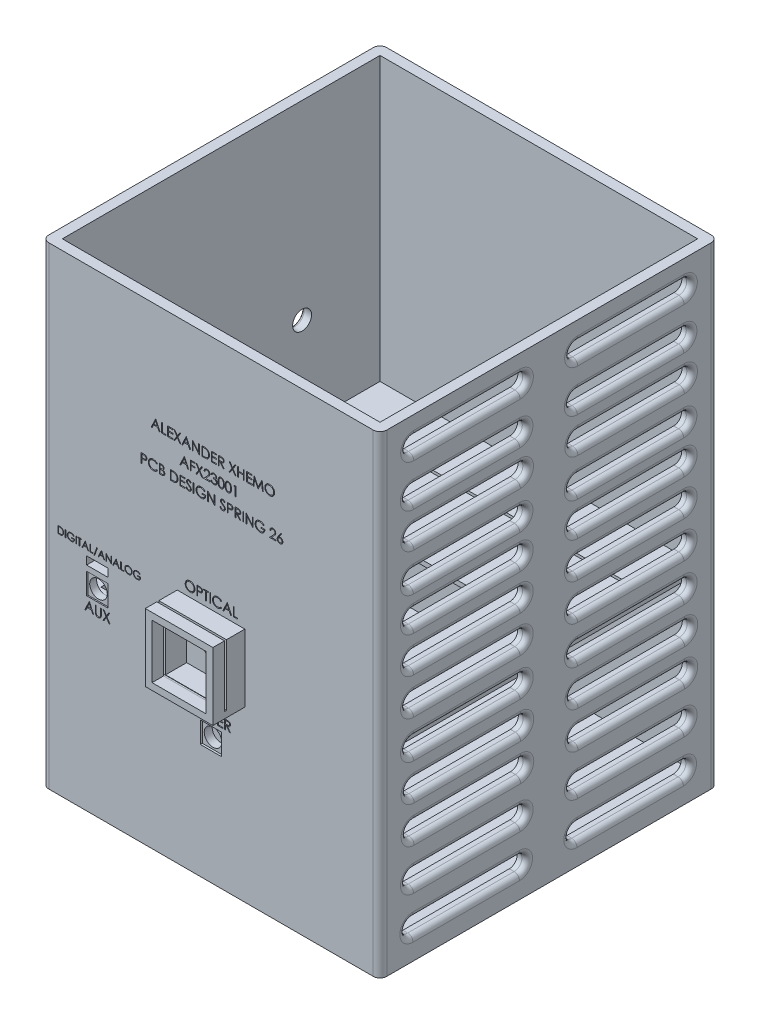
SolidWorks part; units mm, degrees
ref_plane "Front Plane" through (0, 0, 0) normal (0, 0, 1) x (1, 0, 0)
ref_plane "Top Plane" through (0, 0, 0) normal (0, 1, 0) x (1, 0, 0)
ref_plane "Right Plane" through (0, 0, 0) normal (1, 0, 0) x (0, 0, -1)
sketch "Sketch1" plane through (0, 0, 0) normal (0, 1, 0) x (1, 0, 0)
  line L1 (-58.7434, 32.2257) -> (68.2566, 32.2257)
  line L2 (-58.7434, 32.2257) -> (-58.7434, -94.7743)
  line L3 (-58.7434, -94.7743) -> (68.2566, -94.7743)
  line L4 (68.2566, 32.2257) -> (68.2566, -94.7743)
  dimension "D1" = 127
  dimension "D2" = 127
extrude "Boss-Extrude1" add sketch "Sketch1" along normal blind 177.8
sketch "Sketch2" plane through (0, 177.8, 0) normal (0, 1, 0) x (1, 0, 0)
  line L0 (68.2566, 32.2257) -> (-58.7434, 32.2257) construction
  line L1 (-54.9334, 28.4157) -> (64.4466, 28.4157)
  line L2 (-54.9334, 28.4157) -> (-54.9334, -90.9643)
  line L3 (-54.9334, -90.9643) -> (64.4466, -90.9643)
  line L4 (64.4466, 28.4157) -> (64.4466, -90.9643)
  line L5 (-58.7434, 32.2257) -> (-58.7434, -94.7743) construction
  line L6 (68.2566, -94.7743) -> (68.2566, 32.2257) construction
  line L7 (-58.7434, -94.7743) -> (68.2566, -94.7743) construction
  dimension "D1" = 3.81
  dimension "D2" = 3.81
  dimension "D3" = 3.81
  dimension "D4" = 3.81
extrude "Cut-Extrude1" cut sketch "Sketch2" against normal blind 173.99 contours L2 L1 L4 L3
sketch "Sketch3" plane through (68.2566, 0, 0) normal (1, 0, 0) x (0, 0, -1)
  line L6 (-20.4535, 167.6868) -> (19.5465, 167.6868) construction
  line L8 (-82.0743, 167.6822) -> (-42.0743, 167.6822) construction
  line L9 (-82.0743, 170.6109) -> (-42.0743, 170.6109)
  line L10 (-82.0743, 164.7535) -> (-42.0743, 164.7535)
  line L12 (-20.4535, 170.6155) -> (19.5465, 170.6155)
  line L13 (-20.4535, 164.7581) -> (19.5465, 164.7581)
  line L14 (-20.3906, 138.5625) -> (19.6094, 138.5625) construction
  line L15 (-82.0115, 138.558) -> (-42.0115, 138.558) construction
  line L16 (-20.6092, 151.8967) -> (19.3908, 151.8967) construction
  line L17 (-82.2301, 151.8921) -> (-42.2301, 151.8921) construction
  line L18 (-82.2301, 154.8207) -> (-42.2301, 154.8207)
  line L19 (-82.2301, 148.9634) -> (-42.2301, 148.9634)
  line L20 (-20.6092, 154.8253) -> (19.3908, 154.8253)
  line L21 (-20.6092, 148.968) -> (19.3908, 148.968)
  line L22 (-82.0115, 141.4866) -> (-42.0115, 141.4866)
  line L23 (-82.0115, 135.6293) -> (-42.0115, 135.6293)
  line L24 (-20.3906, 141.4912) -> (19.6094, 141.4912)
  line L25 (-20.3906, 135.6339) -> (19.6094, 135.6339)
  line L26 (-20.6092, 124.3541) -> (19.3908, 124.3541) construction
  line L27 (-82.2301, 124.3495) -> (-42.2301, 124.3495) construction
  line L28 (-82.2301, 127.2781) -> (-42.2301, 127.2781)
  line L29 (-82.2301, 121.4208) -> (-42.2301, 121.4208)
  line L30 (-20.6092, 127.2827) -> (19.3908, 127.2827)
  line L31 (-20.6092, 121.4254) -> (19.3908, 121.4254)
  line L32 (-20.5154, 111.5408) -> (19.4846, 111.5408) construction
  line L33 (-82.1363, 111.5362) -> (-42.1363, 111.5362) construction
  line L34 (-82.1363, 114.4648) -> (-42.1363, 114.4648)
  line L35 (-82.1363, 108.6075) -> (-42.1363, 108.6075)
  line L36 (-20.5154, 114.4694) -> (19.4846, 114.4694)
  line L37 (-20.5154, 108.6121) -> (19.4846, 108.6121)
  line L38 (-20.5154, 97.9879) -> (19.4846, 97.9879) construction
  line L39 (-82.1363, 97.9833) -> (-42.1363, 97.9833) construction
  line L40 (-82.1363, 100.912) -> (-42.1363, 100.912)
  line L41 (-82.1363, 95.0547) -> (-42.1363, 95.0547)
  line L42 (-20.5154, 100.9166) -> (19.4846, 100.9166)
  line L43 (-20.5154, 95.0593) -> (19.4846, 95.0593)
  line L44 (-20.5154, 84.2199) -> (19.4846, 84.2199) construction
  line L45 (-82.1363, 84.2153) -> (-42.1363, 84.2153) construction
  line L46 (-82.1363, 87.144) -> (-42.1363, 87.144)
  line L47 (-82.1363, 81.2867) -> (-42.1363, 81.2867)
  line L48 (-20.5154, 87.1486) -> (19.4846, 87.1486)
  line L49 (-20.5154, 81.2913) -> (19.4846, 81.2913)
  line L50 (-20.5154, 70.0217) -> (19.4846, 70.0217) construction
  line L51 (-82.1363, 70.0171) -> (-42.1363, 70.0171) construction
  line L52 (-82.1363, 72.9458) -> (-42.1363, 72.9458)
  line L53 (-82.1363, 67.0885) -> (-42.1363, 67.0885)
  line L54 (-20.5154, 72.9504) -> (19.4846, 72.9504)
  line L55 (-20.5154, 67.0931) -> (19.4846, 67.0931)
  line L56 (-20.3003, 56.2537) -> (19.6997, 56.2537) construction
  line L57 (-81.9211, 56.2491) -> (-41.9211, 56.2491) construction
  line L58 (-81.9211, 59.1778) -> (-41.9211, 59.1778)
  line L59 (-81.9211, 53.3205) -> (-41.9211, 53.3205)
  line L60 (-20.3003, 59.1824) -> (19.6997, 59.1824)
  line L61 (-20.3003, 53.3251) -> (19.6997, 53.3251)
  line L62 (-20.3003, 42.4858) -> (19.6997, 42.4858) construction
  line L63 (-81.9211, 42.4812) -> (-41.9211, 42.4812) construction
  line L64 (-81.9211, 45.4098) -> (-41.9211, 45.4098)
  line L65 (-81.9211, 39.5525) -> (-41.9211, 39.5525)
  line L66 (-20.3003, 45.4144) -> (19.6997, 45.4144)
  line L67 (-20.3003, 39.5571) -> (19.6997, 39.5571)
  line L68 (-20.5436, 26.9383) -> (19.4564, 26.9383) construction
  line L69 (-82.1645, 26.9337) -> (-42.1645, 26.9337) construction
  line L86 (-82.1645, 29.8624) -> (-42.1645, 29.8624)
  line L87 (-82.1645, 24.005) -> (-42.1645, 24.005)
  line L88 (-20.5436, 29.867) -> (19.4564, 29.867)
  line L89 (-20.5436, 24.0096) -> (19.4564, 24.0096)
  line L90 (-20.7544, 11.1247) -> (19.2456, 11.1247) construction
  line L91 (-82.3753, 11.1201) -> (-42.3753, 11.1201) construction
  line L96 (-82.3753, 14.0488) -> (-42.3753, 14.0488)
  line L97 (-82.3753, 8.1915) -> (-42.3753, 8.1915)
  line L98 (-20.7544, 14.0534) -> (19.2456, 14.0534)
  line L99 (-20.7544, 8.1961) -> (19.2456, 8.1961)
  arc A0 (-82.0743, 170.6109) -> (-82.0743, 164.7535) centre (-82.0743, 167.6822) ccw
  arc A1 (-42.0743, 164.7535) -> (-42.0743, 170.6109) centre (-42.0743, 167.6822) ccw
  arc A2 (-20.4535, 170.6155) -> (-20.4535, 164.7581) centre (-20.4535, 167.6868) ccw
  arc A3 (19.5465, 164.7581) -> (19.5465, 170.6155) centre (19.5465, 167.6868) ccw
  arc A4 (-82.2301, 154.8207) -> (-82.2301, 148.9634) centre (-82.2301, 151.8921) ccw
  arc A5 (-42.2301, 148.9634) -> (-42.2301, 154.8207) centre (-42.2301, 151.8921) ccw
  arc A6 (-20.6092, 154.8253) -> (-20.6092, 148.968) centre (-20.6092, 151.8967) ccw
  arc A7 (19.3908, 148.968) -> (19.3908, 154.8253) centre (19.3908, 151.8967) ccw
  arc A8 (-82.0115, 141.4866) -> (-82.0115, 135.6293) centre (-82.0115, 138.558) ccw
  arc A9 (-42.0115, 135.6293) -> (-42.0115, 141.4866) centre (-42.0115, 138.558) ccw
  arc A10 (-20.3906, 141.4912) -> (-20.3906, 135.6339) centre (-20.3906, 138.5625) ccw
  arc A11 (19.6094, 135.6339) -> (19.6094, 141.4912) centre (19.6094, 138.5625) ccw
  arc A12 (-82.2301, 127.2781) -> (-82.2301, 121.4208) centre (-82.2301, 124.3495) ccw
  arc A13 (-42.2301, 121.4208) -> (-42.2301, 127.2781) centre (-42.2301, 124.3495) ccw
  arc A14 (-20.6092, 127.2827) -> (-20.6092, 121.4254) centre (-20.6092, 124.3541) ccw
  arc A15 (19.3908, 121.4254) -> (19.3908, 127.2827) centre (19.3908, 124.3541) ccw
  arc A16 (-82.1363, 114.4648) -> (-82.1363, 108.6075) centre (-82.1363, 111.5362) ccw
  arc A17 (-42.1363, 108.6075) -> (-42.1363, 114.4648) centre (-42.1363, 111.5362) ccw
  arc A18 (-20.5154, 114.4694) -> (-20.5154, 108.6121) centre (-20.5154, 111.5408) ccw
  arc A19 (19.4846, 108.6121) -> (19.4846, 114.4694) centre (19.4846, 111.5408) ccw
  arc A20 (-82.1363, 100.912) -> (-82.1363, 95.0547) centre (-82.1363, 97.9833) ccw
  arc A21 (-42.1363, 95.0547) -> (-42.1363, 100.912) centre (-42.1363, 97.9833) ccw
  arc A22 (-20.5154, 100.9166) -> (-20.5154, 95.0593) centre (-20.5154, 97.9879) ccw
  arc A23 (19.4846, 95.0593) -> (19.4846, 100.9166) centre (19.4846, 97.9879) ccw
  arc A24 (-82.1363, 87.144) -> (-82.1363, 81.2867) centre (-82.1363, 84.2153) ccw
  arc A25 (-42.1363, 81.2867) -> (-42.1363, 87.144) centre (-42.1363, 84.2153) ccw
  arc A26 (-20.5154, 87.1486) -> (-20.5154, 81.2913) centre (-20.5154, 84.2199) ccw
  arc A27 (19.4846, 81.2913) -> (19.4846, 87.1486) centre (19.4846, 84.2199) ccw
  arc A28 (-82.1363, 72.9458) -> (-82.1363, 67.0885) centre (-82.1363, 70.0171) ccw
  arc A29 (-42.1363, 67.0885) -> (-42.1363, 72.9458) centre (-42.1363, 70.0171) ccw
  arc A30 (-20.5154, 72.9504) -> (-20.5154, 67.0931) centre (-20.5154, 70.0217) ccw
  arc A31 (19.4846, 67.0931) -> (19.4846, 72.9504) centre (19.4846, 70.0217) ccw
  arc A32 (-81.9211, 59.1778) -> (-81.9211, 53.3205) centre (-81.9211, 56.2491) ccw
  arc A33 (-41.9211, 53.3205) -> (-41.9211, 59.1778) centre (-41.9211, 56.2491) ccw
  arc A34 (-20.3003, 59.1824) -> (-20.3003, 53.3251) centre (-20.3003, 56.2537) ccw
  arc A35 (19.6997, 53.3251) -> (19.6997, 59.1824) centre (19.6997, 56.2537) ccw
  arc A36 (-81.9211, 45.4098) -> (-81.9211, 39.5525) centre (-81.9211, 42.4812) ccw
  arc A37 (-41.9211, 39.5525) -> (-41.9211, 45.4098) centre (-41.9211, 42.4812) ccw
  arc A38 (-20.3003, 45.4144) -> (-20.3003, 39.5571) centre (-20.3003, 42.4858) ccw
  arc A39 (19.6997, 39.5571) -> (19.6997, 45.4144) centre (19.6997, 42.4858) ccw
  arc A56 (-82.1645, 29.8624) -> (-82.1645, 24.005) centre (-82.1645, 26.9337) ccw
  arc A57 (-42.1645, 24.005) -> (-42.1645, 29.8624) centre (-42.1645, 26.9337) ccw
  arc A58 (-20.5436, 29.867) -> (-20.5436, 24.0096) centre (-20.5436, 26.9383) ccw
  arc A59 (19.4564, 24.0096) -> (19.4564, 29.867) centre (19.4564, 26.9383) ccw
  arc A64 (-82.3753, 14.0488) -> (-82.3753, 8.1915) centre (-82.3753, 11.1201) ccw
  arc A65 (-42.3753, 8.1915) -> (-42.3753, 14.0488) centre (-42.3753, 11.1201) ccw
  arc A66 (-20.7544, 14.0534) -> (-20.7544, 8.1961) centre (-20.7544, 11.1247) ccw
  arc A67 (19.2456, 8.1961) -> (19.2456, 14.0534) centre (19.2456, 11.1247) ccw
  point P4 (-62.0743, 167.6822)
  point P23 (-0.4535, 167.6868)
  point P31 (-62.2301, 151.8921)
  point P39 (-0.6092, 151.8967)
  point P46 (-62.0115, 138.558)
  point P53 (-0.3906, 138.5625)
  point P60 (-62.2301, 124.3495)
  point P67 (-0.6092, 124.3541)
  point P74 (-62.1363, 111.5362)
  point P81 (-0.5154, 111.5408)
  point P88 (-62.1363, 97.9833)
  point P95 (-0.5154, 97.9879)
  point P102 (-62.1363, 84.2153)
  point P109 (-0.5154, 84.2199)
  point P116 (-62.1363, 70.0171)
  point P123 (-0.5154, 70.0217)
  point P130 (-61.9211, 56.2491)
  point P137 (-0.3003, 56.2537)
  point P144 (-61.9211, 42.4812)
  point P151 (-0.3003, 42.4858)
  point P158 (-62.1645, 26.9337)
  point P165 (-0.5436, 26.9383)
  point P172 (-62.3753, 11.1201)
  point P179 (-0.7544, 11.1247)
extrude "Cut-Extrude2" cut sketch "Sketch3" against normal blind 6.35
fillet "Fillet2" radius 2 96 edges at (68.2566, 167.6822, 85.003) (68.2566, 170.6109, 62.0743) (68.2566, 167.6822, 39.1457) (68.2566, 167.6868, 23.3821) (68.2566, 170.6155, 0.4535) (68.2566, 167.6868, -22.4752) (68.2566, 151.8921, 85.1587) (68.2566, 154.8207, 62.2301) (68.2566, 151.8921, 39.3014) (68.2566, 151.8967, 23.5379) (68.2566, 154.8253, 0.6092) (68.2566, 151.8967, -22.3195) (68.2566, 138.5625, 23.3193) (68.2566, 141.4912, 0.3906) (68.2566, 138.5625, -22.5381) (68.2566, 138.558, 84.9401) (68.2566, 141.4866, 62.0115) (68.2566, 138.558, 39.0828) (68.2566, 124.3495, 85.1587) (68.2566, 127.2781, 62.2301) (68.2566, 124.3495, 39.3014) (68.2566, 124.3541, 23.5379) (68.2566, 127.2827, 0.6092) (68.2566, 124.3541, -22.3195) (68.2566, 111.5362, 85.0649) (68.2566, 114.4648, 62.1363) (68.2566, 111.5362, 39.2076) (68.2566, 111.5408, 23.444) (68.2566, 114.4694, 0.5154) (68.2566, 111.5408, -22.4133) (68.2566, 97.9879, 23.444) (68.2566, 100.9166, 0.5154) (68.2566, 97.9879, -22.4133) (68.2566, 97.9833, 85.0649) (68.2566, 100.912, 62.1363) (68.2566, 97.9833, 39.2076) (68.2566, 84.2153, 85.0649) (68.2566, 87.144, 62.1363) (68.2566, 84.2153, 39.2076) (68.2566, 84.2199, 23.444) (68.2566, 87.1486, 0.5154) (68.2566, 84.2199, -22.4133) (68.2566, 70.0217, 23.444) (68.2566, 72.9504, 0.5154) (68.2566, 70.0217, -22.4133) (68.2566, 70.0171, 85.0649) (68.2566, 72.9458, 62.1363) (68.2566, 70.0171, 39.2076) (68.2566, 56.2491, 84.8498) (68.2566, 59.1778, 61.9211) (68.2566, 56.2491, 38.9925) (68.2566, 56.2537, 23.2289) (68.2566, 59.1824, 0.3003) (68.2566, 56.2537, -22.6284) (68.2566, 42.4858, 23.2289) (68.2566, 45.4144, 0.3003) (68.2566, 42.4858, -22.6284) (68.2566, 42.4812, 84.8498) (68.2566, 45.4098, 61.9211) (68.2566, 42.4812, 38.9925) (68.2566, 26.9337, 85.0931) (68.2566, 29.8624, 62.1645) (68.2566, 26.9337, 39.2358) (68.2566, 26.9383, 23.4722) (68.2566, 29.867, 0.5436) (68.2566, 26.9383, -22.3851) (68.2566, 11.1247, 23.6831) (68.2566, 14.0534, 0.7544) (68.2566, 11.1247, -22.1742) (68.2566, 11.1201, 85.304) (68.2566, 14.0488, 62.3753) (68.2566, 11.1201, 39.4467) (68.2566, 164.7535, 62.0743) (68.2566, 164.7581, 0.4535) (68.2566, 148.9634, 62.2301) (68.2566, 148.968, 0.6092) (68.2566, 135.6339, 0.3906) (68.2566, 135.6293, 62.0115) (68.2566, 121.4208, 62.2301) (68.2566, 121.4254, 0.6092) (68.2566, 108.6075, 62.1363) (68.2566, 108.6121, 0.5154) (68.2566, 95.0593, 0.5154) (68.2566, 95.0547, 62.1363) (68.2566, 81.2867, 62.1363) (68.2566, 81.2913, 0.5154) (68.2566, 67.0931, 0.5154) (68.2566, 67.0885, 62.1363) (68.2566, 53.3205, 61.9211) (68.2566, 53.3251, 0.3003) (68.2566, 39.5571, 0.3003) (68.2566, 39.5525, 61.9211) (68.2566, 24.005, 62.1645) (68.2566, 24.0096, 0.5436) (68.2566, 8.1961, 0.7544) (68.2566, 8.1915, 62.3753)
fillet "Fillet3" radius 2.54 4 edges at (68.2566, 88.9, -32.2257) (68.2566, 88.9, 94.7743) (-58.7434, 88.9, -32.2257) (-58.7434, 88.9, 94.7743)
sketch "Sketch4" plane through (0, 0, -32.2257) normal (0, 0, -1) x (-1, 0, 0)
  line L7 (7.9434, 76.2) -> (7.9434, 88.9)
  line L8 (7.9434, 76.2) -> (7.9434, 63.5)
  line L10 (-17.4566, 76.2) -> (-17.4566, 88.9)
  line L11 (-17.4566, 88.9) -> (7.9434, 88.9)
  line L12 (-17.4566, 76.2) -> (-17.4566, 63.5)
  line L13 (-17.4566, 63.5) -> (7.9434, 63.5)
extrude "Boss-Extrude2" add sketch "Sketch4" along normal blind 20
sketch "Sketch6" plane through (-7.9434, 0, 0) normal (-1, 0, 0) x (0, 0, 1)
  line L0 (-52.2257, 63.5) -> (-32.2257, 63.5)
  line L1 (-32.2257, 63.5) -> (-32.2257, 46.1669)
  line L2 (-32.2257, 46.1669) -> (-52.2257, 63.5)
extrude "Boss-Extrude4" add sketch "Sketch6" against normal blind 25.4
sketch "Sketch8" plane through (0, 0, -52.2257) normal (0, 0, -1) x (-1, 0, 0)
  line L0 (1.5934, 63.5) -> (1.5934, 88.9) construction
  line L2 (-11.1066, 40.0423) -> (-11.1066, 100.629) construction
  line L3 (-68.2566, 76.2) -> (58.7434, 76.2) construction
  line L6 (-65.7166, 0) -> (56.2034, 0) construction
  circle A0 centre (-11.1066, 76.2) radius 3.175
  dimension "D3" = 6.35
  dimension "D1" = 76.2
  dimension "D2" = 12.7
extrude "Cut-Extrude4" cut sketch "Sketch8" against normal blind 50.8
sketch "Sketch10" plane through (-7.9434, 0, 0) normal (-1, 0, 0) x (0, 0, 1)
  line L0 (-52.2257, 76.2) -> (-32.2257, 76.2) construction
  line L4 (-42.2257, 88.9) -> (-42.2257, 54.8334) construction
  circle A0 centre (-42.196, 76.2) radius 3.175
  dimension "D1" = 6.35
extrude "Cut-Extrude5" cut sketch "Sketch10" against normal blind 20
sketch "Sketch11" plane through (-58.7434, 0, 0) normal (-1, 0, 0) x (0, 0, 1)
  line L1 (-4.2857, 68.18) -> (66.8343, 68.18)
  line L2 (-4.2857, 68.18) -> (-4.2857, 25)
  line L3 (-4.2857, 25) -> (66.8343, 25)
  line L4 (66.8343, 68.18) -> (66.8343, 25)
extrude "Cut-Extrude6" cut sketch "Sketch11" against normal blind 1.25
sketch "Sketch12" plane through (-57.4934, 0, 0) normal (-1, 0, 0) x (0, 0, 1)
  line L0 (17.1271, 68.18) -> (45.2384, 68.18)
  line L1 (66.8343, 68.18) -> (52.8643, 68.18)
  line L2 (66.8343, 68.18) -> (-4.2857, 68.18) construction
  line L3 (17.1271, 25) -> (45.2384, 25)
  line L4 (-4.2857, 68.18) -> (9.6843, 68.18)
  line L6 (17.1271, 68.18) -> (17.1271, 25)
  line L7 (45.2384, 25) -> (45.2384, 68.18)
  circle A0 centre (17.1271, 46.59) radius 21.59
  circle A1 centre (45.2384, 46.59) radius 21.59
  dimension "D1" = 28.1113
  dimension "D2" = 13.97
  dimension "D3" = 13.97
extrude "Cut-Extrude7" cut sketch "Sketch12" against normal blind 14.25 contours A0 | A1 | L7 L0 L6 L3
sketch "Sketch13" plane through (-57.4934, 0, 0) normal (-1, 0, 0) x (0, 0, 1)
  line L0 (-4.2857, 55.2093) -> (6.4207, 68.18)
  line L1 (-4.2857, 68.18) -> (-4.2857, 49.3507) construction
  line L2 (17.1271, 68.18) -> (-4.2857, 68.18) construction
  line L3 (6.4207, 68.18) -> (17.1271, 68.18)
  line L4 (17.1271, 68.18) -> (-4.2857, 49.3507)
  line L5 (-4.2857, 49.3507) -> (-4.2857, 55.2093)
  line L11 (-4.2857, 43.8293) -> (17.1271, 25)
  line L12 (55.0973, 25) -> (66.0345, 37.4378)
  line L13 (45.2384, 25) -> (66.8343, 25) construction
  line L14 (66.0345, 37.4378) -> (66.521, 42.9595)
  line L15 (66.521, 42.9595) -> (45.2384, 25)
  line L16 (45.2384, 25) -> (55.0973, 25)
  line L17 (66.521, 50.2205) -> (66.521, 57.1453)
  line L18 (66.521, 57.1453) -> (53.3746, 68.18)
  line L19 (66.8343, 68.18) -> (45.2384, 68.18) construction
  line L20 (53.3746, 68.18) -> (45.2384, 68.18)
  line L21 (45.2384, 68.18) -> (66.521, 50.2205)
  line L22 (-4.2857, 43.8293) -> (-4.2857, 38.2927)
  line L23 (-4.2857, 43.8293) -> (-4.2857, 25) construction
  line L24 (-4.2857, 38.2927) -> (-4.2857, 37.4378)
  line L25 (-4.2857, 37.4378) -> (8.2172, 25)
  line L26 (-4.2857, 25) -> (17.1271, 25) construction
  line L27 (8.2172, 25) -> (17.1271, 25)
  arc A0 (17.1271, 68.18) -> (-4.2857, 49.3507) centre (17.1271, 46.59) ccw construction
  arc A1 (-4.2857, 43.8293) -> (17.1271, 25) centre (17.1271, 46.59) ccw construction
  arc A2 (45.2384, 25) -> (45.2384, 68.18) centre (45.2384, 46.59) ccw construction
extrude "Cut-Extrude8" cut sketch "Sketch13" against normal blind 14.25
sketch "Sketch14" plane through (-57.4934, 0, 0) normal (-1, 0, 0) x (0, 0, 1)
  line L0 (66.521, 57.1453) -> (66.8343, 57.1453)
  line L1 (66.8343, 25) -> (66.8343, 68.18) construction
  line L2 (66.8343, 57.1453) -> (66.8343, 37.4378)
  line L3 (66.8343, 37.4378) -> (66.0345, 37.4378)
  line L4 (66.0345, 37.4378) -> (66.521, 57.1453)
extrude "Cut-Extrude9" cut sketch "Sketch14" against normal blind 14.25
sketch "Sketch15" plane through (0, 0, -28.4157) normal (0, 0, 1) x (1, 0, 0)
  line L6 (11.0802, 71.7154) -> (64.4466, 71.7154)
  line L7 (64.4466, 3.81) -> (64.4466, 177.8) construction
  line L8 (64.4466, 71.7154) -> (64.4466, 68.936)
  line L9 (64.4466, 68.936) -> (-54.9334, 68.936)
  line L10 (-54.9334, 3.81) -> (-54.9334, 177.8) construction
  line L11 (-54.9334, 68.936) -> (-54.9334, 71.7154)
  line L12 (-54.9334, 71.7154) -> (11.0802, 71.7154)
extrude "Boss-Extrude6" add sketch "Sketch15" along normal blind 122
sketch "Sketch16" plane through (0, 71.7154, 0) normal (0, 1, 0) x (1, 0, 0)
  line L1 (-54.9334, -90.9643) -> (64.4466, -90.9643) construction
  line L4 (54.9466, -90.9643) -> (-45.4334, -90.9643)
  line L5 (54.9466, -90.9643) -> (54.9466, 9.4459)
  line L6 (54.9466, 9.4459) -> (-45.4334, 9.4459)
  line L7 (-45.4334, -90.9643) -> (-45.4334, 9.4459)
extrude "Cut-Extrude10" cut sketch "Sketch16" against normal blind 1
sketch "Sketch17" plane through (0, 0, 94.7743) normal (0, 0, 1) x (1, 0, 0)
  line L1 (17.4566, 76.2) -> (17.4566, 88.9)
  line L2 (17.4566, 76.2) -> (17.4566, 63.5)
  line L4 (17.4566, 88.9) -> (4.7566, 88.9)
  line L5 (4.7566, 88.9) -> (-7.9434, 88.9)
  line L6 (-7.9434, 88.9) -> (-7.9434, 63.5)
  line L7 (-7.9434, 63.5) -> (17.4566, 63.5)
extrude "Boss-Extrude8" add sketch "Sketch17" along normal blind 12
sketch "Sketch19" plane through (0, 0, 106.7743) normal (0, 0, 1) x (1, 0, 0)
  line L0 (17.4566, 88.9) -> (-7.9434, 88.9) construction
  line L1 (14.9166, 86.36) -> (-5.4034, 86.36)
  line L2 (14.9166, 86.36) -> (14.9166, 66.04)
  line L3 (14.9166, 66.04) -> (-5.4034, 66.04)
  line L4 (-5.4034, 86.36) -> (-5.4034, 66.04)
  line L5 (-7.9434, 63.5) -> (17.4566, 63.5) construction
  line L6 (17.4566, 63.5) -> (17.4566, 88.9) construction
  line L7 (-7.9434, 88.9) -> (-7.9434, 63.5) construction
  dimension "D1" = 2.54
  dimension "D2" = 2.54
  dimension "D3" = 2.54
  dimension "D4" = 2.54
extrude "Cut-Extrude12" cut sketch "Sketch19" against normal blind 13
sketch "Sketch20" plane through (0, 88.9, 0) normal (0, 1, 0) x (1, 0, 0)
  line L0 (-7.9434, -106.7743) -> (-7.9434, -94.7743) construction
  line L1 (-7.9434, -101.6869) -> (17.4566, -101.6869)
  line L2 (-7.9434, -101.6869) -> (-7.9434, -102.4274)
  line L3 (-7.9434, -102.4274) -> (17.4566, -102.4274)
  line L4 (17.4566, -101.6869) -> (17.4566, -102.4274)
  line L5 (17.4566, -106.7743) -> (17.4566, -94.7743) construction
extrude "Cut-Extrude13" cut sketch "Sketch20" against normal blind 23
sketch "Sketch21" plane through (0, 0, 94.7743) normal (0, 0, 1) x (1, 0, 0)
  line L0 (4.7566, 0) -> (4.7566, 177.8) construction
  line L3 (14.9166, 76.2) -> (-56.2034, 76.2) construction
  circle A0 centre (4.7566, 76.2052) radius 4.5126
extrude "Cut-Extrude14" cut sketch "Sketch21" against normal blind 23
sketch "Sketch24" plane through (-58.7434, 0, 0) normal (-1, 0, 0) x (0, 0, 1)
  circle A0 centre (0.8623, 106.28) radius 3.556
  circle A1 centre (31.2743, 106.28) radius 3.556
  circle A2 centre (61.704, 106.28) radius 3.556
extrude "Cut-Extrude16" cut sketch "Sketch24" against normal blind 42
fillet "Fillet4" radius 1 3 edges at (-58.7434, 106.28, 4.4183) (-58.7434, 106.28, 34.8303) (-58.7434, 106.28, 65.26)
fillet "Fillet5" radius 0.5 4 edges at (-57.4934, 31.2189, 1.9658) (-57.4934, 31.2189, 60.5659) (-57.4934, 62.6626, 59.9478) (-57.4934, 61.6946, 1.0675)
sketch "Sketch26" plane through (0, 0, 90.9643) normal (0, 0, -1) x (-1, 0, 0)
  line L1 (45.4334, 70.7154) -> (-54.9466, 70.7154) construction
  line L2 (43.4334, 70.7154) -> (43.4334, 77.3154)
  line L3 (43.4334, 77.3154) -> (32.4334, 77.3154)
  line L4 (32.4334, 77.3154) -> (32.4334, 70.7154)
  line L5 (32.4334, 70.7154) -> (37.9334, 70.7154)
  line L6 (37.9334, 70.7154) -> (43.4334, 70.7154)
extrude "Cut-Extrude18" cut sketch "Sketch26" against normal blind 0.75 contours L2 L3 L4 L5 L6
sketch "Sketch27" plane through (0, 0, 91.7143) normal (0, 0, -1) x (-1, 0, 0)
  circle A0 centre (37.981, 74.0154) radius 3.3003
extrude "Cut-Extrude19" cut sketch "Sketch27" against normal blind 4.75 contours A0
sketch "Sketch28" plane through (0, 0, 94.7743) normal (0, 0, 1) x (1, 0, 0)
  line L1 (-41.981, 78.0154) -> (-33.981, 78.0154)
  line L2 (-41.981, 78.0154) -> (-41.981, 70.0154)
  line L3 (-41.981, 70.0154) -> (-33.981, 70.0154)
  line L4 (-33.981, 78.0154) -> (-33.981, 70.0154)
  circle A2 centre (-37.981, 74.0154) radius 3.3003 construction
  dimension "D1" = 4
  dimension "D2" = 4
extrude "Cut-Extrude20" cut sketch "Sketch28" against normal blind 0.45
sketch "Sketch29" plane through (0, 70.7154, 0) normal (0, 1, 0) x (1, 0, 0)
  line L0 (-32.4334, -90.9643) -> (54.9466, -90.9643) construction
  line L1 (-41.4334, -89.9643) -> (31.3166, -89.9643)
  line L2 (-41.4334, -89.9643) -> (-41.4334, -20.7143)
  line L3 (-41.4334, -20.7143) -> (31.3166, -20.7143)
  line L4 (31.3166, -89.9643) -> (31.3166, -20.7143)
  line L5 (-45.4334, 9.4459) -> (-45.4334, -90.9643) construction
  dimension "D1" = 1
  dimension "D2" = 69.25
  dimension "D3" = 4
  dimension "D4" = 72.75
extrude "Cut-Extrude21" cut sketch "Sketch29" against normal blind 10
sketch "Sketch30" plane through (0, 0, 94.7743) normal (0, 0, 1) x (1, 0, 0)
  line L3 (-41.981, 80.0198) -> (-33.981, 80.0198)
  line L4 (-41.981, 80.0198) -> (-41.981, 83.0198)
  line L5 (-41.981, 83.0198) -> (-33.981, 83.0198)
  line L6 (-33.981, 80.0198) -> (-33.981, 83.0198)
  dimension "D1" = 3
extrude "Cut-Extrude22" cut sketch "Sketch30" against normal blind 10
sketch "Sketch31" plane through (-58.7434, 0, 0) normal (-1, 0, 0) x (0, 0, 1)
  line L0 (46.0138, 113.1815) -> (-29.6857, 113.1815) construction
  line L2 (31.2743, 106.28) -> (31.2743, 165.1889) construction
  line L3 (61.704, 106.28) -> (61.704, 130.3448) construction
  text T0 "VOLUME"
  text T1 "AUX"
  text T2 "LASER"
extrude "Cut-Extrude23" cut sketch "Sketch31" against normal blind 0.5
sketch "Sketch32" plane through (-58.7434, 0, 0) normal (-1, 0, 0) x (0, 0, 1)
  text T0 "<b>OMNI-SONUS</b>" font "Century Gothic" height in points 36
extrude "Cut-Extrude24" cut sketch "Sketch32" against normal blind 0.5
sketch "Sketch33" plane through (0, 0, -32.2257) normal (0, 0, -1) x (-1, 0, 0)
  text T0 "LASERS"
extrude "Cut-Extrude25" cut sketch "Sketch33" against normal blind 0.5
sketch "Sketch34" plane through (0, 0, 94.7743) normal (0, 0, 1) x (1, 0, 0)
  text T0 "AUX"
  text T1 "DIGITAL/ANALOG" font "Century Gothic" height in points 10
extrude "Cut-Extrude26" cut sketch "Sketch34" against normal blind 0.5
sketch "Sketch35" plane through (0, 0, 94.7743) normal (0, 0, 1) x (1, 0, 0)
  text T0 "OPTICAL"
extrude "Cut-Extrude27" cut sketch "Sketch35" against normal blind 0.5
sketch "Sketch36" plane through (0, 0, 94.7743) normal (0, 0, 1) x (1, 0, 0)
  line L0 (0.7566, 51) -> (8.7566, 51)
  line L4 (8.7566, 51) -> (8.7566, 43)
  line L6 (0.7566, 51) -> (0.7566, 43)
  line L7 (0.7566, 43) -> (8.7566, 43)
extrude "Cut-Extrude29" cut sketch "Sketch36" against normal blind 0.75
sketch "Sketch37" plane through (0, 0, 94.0243) normal (0, 0, 1) x (1, 0, 0)
  circle A1 centre (4.7566, 47) radius 3.3
extrude "Cut-Extrude30" cut sketch "Sketch37" against normal blind 3
sketch "Sketch38" plane through (0, 0, 94.7743) normal (0, 0, 1) x (1, 0, 0)
  text T0 "POWER"
extrude "Cut-Extrude31" cut sketch "Sketch38" against normal blind 0.5
sketch "Sketch39" plane through (0, 0, 94.7743) normal (0, 0, 1) x (1, 0, 0)
  text T0 "   ALEXANDER XHEMO\r\n           AFX23001\r\nPCB DESIGN SPRING 26"
extrude "Cut-Extrude32" cut sketch "Sketch39" against normal blind 0.5
